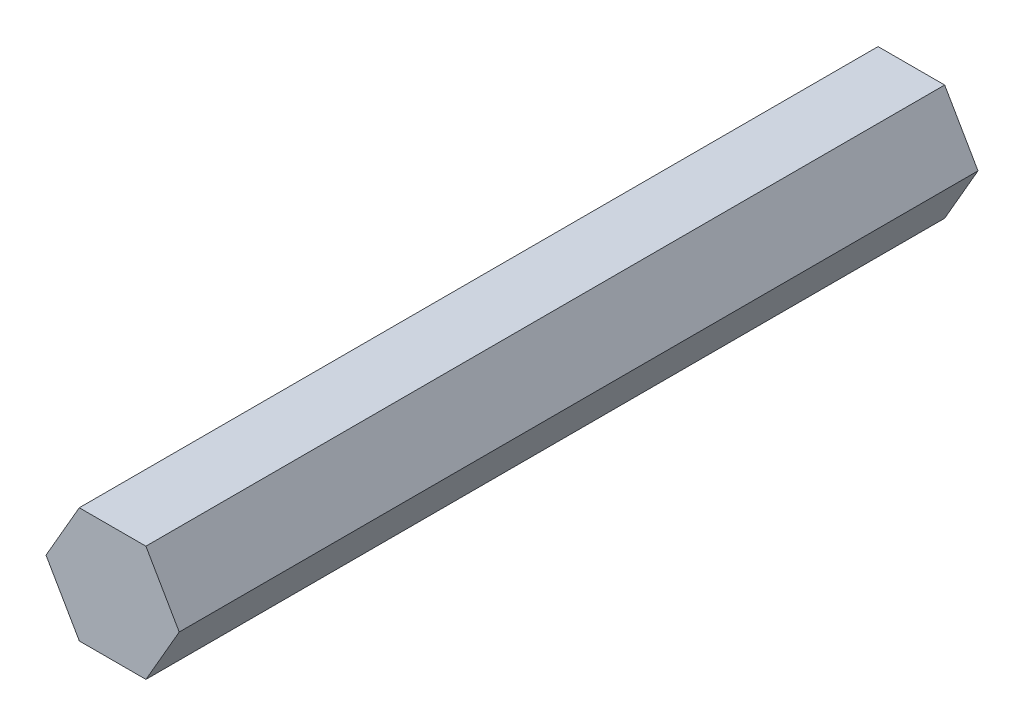
SolidWorks part; units mm, degrees
ref_plane "Front Plane" through (0, 0, 0) normal (0, 0, 1) x (1, 0, 0)
ref_plane "Top Plane" through (0, 0, 0) normal (0, 1, 0) x (1, 0, 0)
ref_plane "Right Plane" through (0, 0, 0) normal (1, 0, 0) x (0, 0, -1)
sketch "Sketch1" plane through (0, 0, 0) normal (0, 0, 1) x (1, 0, 0)
  line L1 (-12.7091, -0.0053) -> (-6.35, -11.009)
  line L2 (-6.35, -11.009) -> (6.3591, -11.0038)
  line L3 (6.3591, -11.0038) -> (12.7091, 0.0053)
  line L4 (12.7091, 0.0053) -> (6.35, 11.009)
  line L5 (6.35, 11.009) -> (-6.3591, 11.0038)
  line L6 (-6.3591, 11.0038) -> (-12.7091, -0.0053)
  circle A0 centre (0, 0) radius 11.0064 construction
  dimension "D1" = 12.7
extrude "Boss-Extrude1" add sketch "Sketch1" along normal blind 152.4
